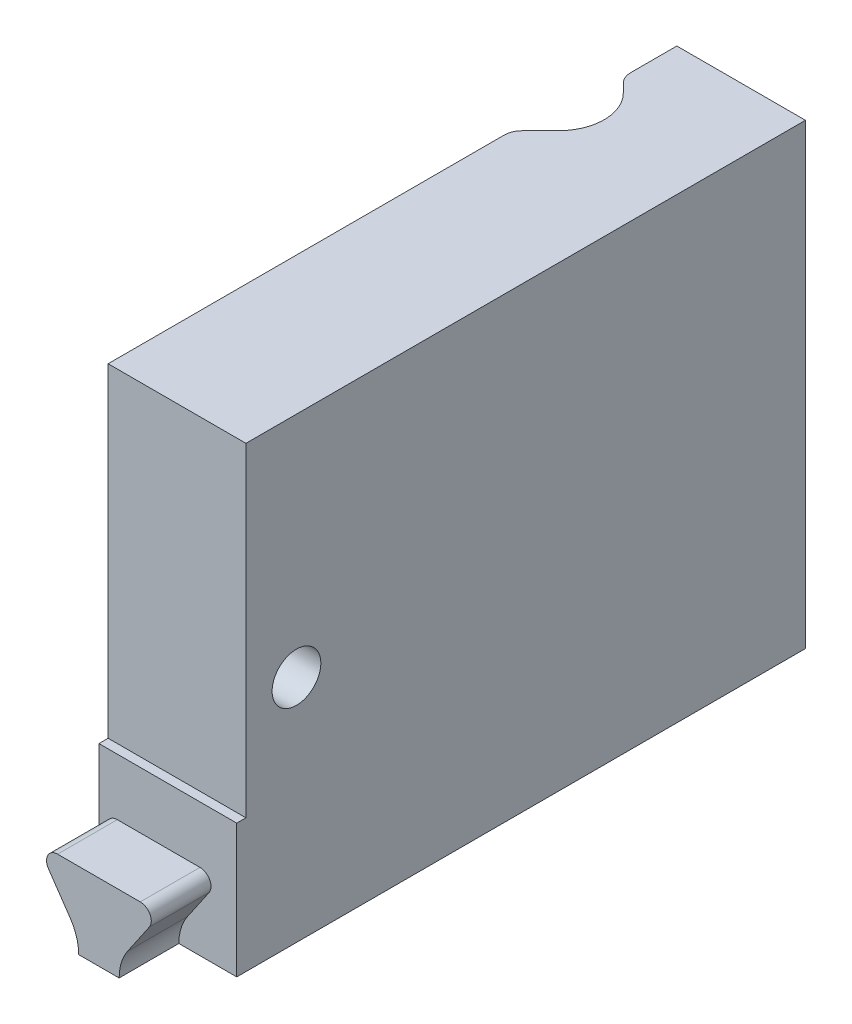
SolidWorks part; units mm, degrees
ref_plane "Front Plane" through (0, 0, 0) normal (0, 0, 1) x (1, 0, 0)
ref_plane "Top Plane" through (0, 0, 0) normal (0, 1, 0) x (1, 0, 0)
ref_plane "Right Plane" through (0, 0, 0) normal (1, 0, 0) x (0, 0, -1)
sketch "Sketch1" plane through (0, 0, 0) normal (0, 0, 1) x (1, 0, 0)
  line L1 (0, 0) -> (-15, 0)
  line L2 (0, 0) -> (0, 14.5)
  line L4 (-15, 0) -> (-15, 14.5)
  line L9 (0, 14.5) -> (-15, 14.5)
  dimension "D2" = 15
  dimension "D3" = 14.5
extrude "Offset" add sketch "Sketch1" along normal blind 1
sketch "Sketch13" plane through (0, 0, 1) normal (0, 0, 1) x (1, 0, 0)
  line L4 (-10.7, 0) -> (-6.3, 0)
  line L7 (-11.6264, 2.9936) -> (-13.9903, 6.4472)
  line L8 (-13, 8.325) -> (-4, 8.325)
  line L12 (-3.0097, 6.4472) -> (-5.3736, 2.9936)
  line L13 (-11.6264, 2.9936) -> (-13.9903, 6.4472)
  line L14 (-13, 8.325) -> (-4, 8.325)
  line L15 (-3.0097, 6.4472) -> (-5.3736, 2.9936)
  arc A8 (-10.7, 0) -> (-11.6264, 2.9936) centre (-16, 0) ccw
  arc A9 (-13, 8.325) -> (-13.9903, 6.4472) centre (-13, 7.125) ccw
  arc A10 (-3.0097, 6.4472) -> (-4, 8.325) centre (-4, 7.125) ccw
  arc A11 (-5.3736, 2.9936) -> (-6.3, 0) centre (-1, 0) ccw
  arc A16 (-10.7, 0) -> (-11.6264, 2.9936) centre (-16, 0) ccw
  arc A17 (-13, 8.325) -> (-13.9903, 6.4472) centre (-13, 7.125) ccw
  arc A18 (-3.0097, 6.4472) -> (-4, 8.325) centre (-4, 7.125) ccw
  arc A19 (-5.3736, 2.9936) -> (-6.3, 0) centre (-1, 0) ccw
  dimension "D1" = 0.3
extrude "Dovetail" add sketch "Sketch13" along normal up to surface (6.5 mm away)
sketch "Sketch5" plane through (0, 0, 0) normal (0, 0, -1) x (-1, 0, 0)
  line L0 (15, 14.5) -> (15, 0) construction
  line L1 (0, 0) -> (15, 0)
  line L2 (0, 0) -> (0, 49.8)
  line L3 (0, 49.8) -> (15, 49.8)
  line L4 (15, 0) -> (15, 49.8)
  line L5 (0, 0) -> (15, 49.8) construction
  line L6 (0, 49.8) -> (15, 0) construction
  line L7 (108.1284, 50) -> (-12.8716, 50) construction
  point P4 (7.5, 24.9)
  dimension "D1" = 0.2
extrude "Base" add sketch "Sketch5" along normal blind 15
sketch "Sketch6" plane through (0, 0, 0) normal (0, -1, 0) x (1, 0, 0)
  line L2 (0, -15) -> (-15, -15) construction
  line L3 (0, -15) -> (-15, -15)
  line L8 (-15, -15) -> (-15, -43.1005)
  line L12 (-14.4142, -44.5147) -> (-12.4645, -46.4645)
  line L13 (-12.4645, -53.5355) -> (-13.4142, -54.4853)
  line L14 (-14, -55.8995) -> (-14, -60.8995)
  line L15 (-14, -60.8995) -> (0, -60.8995)
  line L18 (0, -60.8995) -> (0, -15)
  line L20 (0, 1) -> (0, -15) construction
  arc A5 (-12.4645, -46.4645) -> (-12.4645, -53.5355) centre (-16, -50) cw
  arc A6 (-13.4142, -54.4853) -> (-14, -55.8995) centre (-12, -55.8995) ccw
  arc A7 (-15, -43.1005) -> (-14.4142, -44.5147) centre (-13, -43.1005) ccw
  point P15 (-8.9289, -50)
  dimension "D1" = 5
  dimension "D2" = 2
  dimension "D3" = 35
  dimension "D4" = 1
  dimension "D5" = 1
  dimension "D6" = 5
extrude "Gripping" add sketch "Sketch6" against normal up to surface (49.8 mm away) up to face at (-7.5, 49.8, -7.5)
sketch "Sketch11" plane through (-15, 0, 0) normal (-1, 0, 0) x (0, 0, 1)
  line L1 (13, 50) -> (13, 0) construction
  line L7 (-11, 50) -> (7.5, 50) construction
  line L8 (-11, 0) -> (7.5, 0) construction
  circle A7 centre (-5.5, 25) radius 2.65 construction
  circle A8 centre (-5.5, 25) radius 2.65
  dimension "D1" = 5.3
extrude "ShaftHole" cut sketch "Sketch11" against normal through all both and the other way through all
